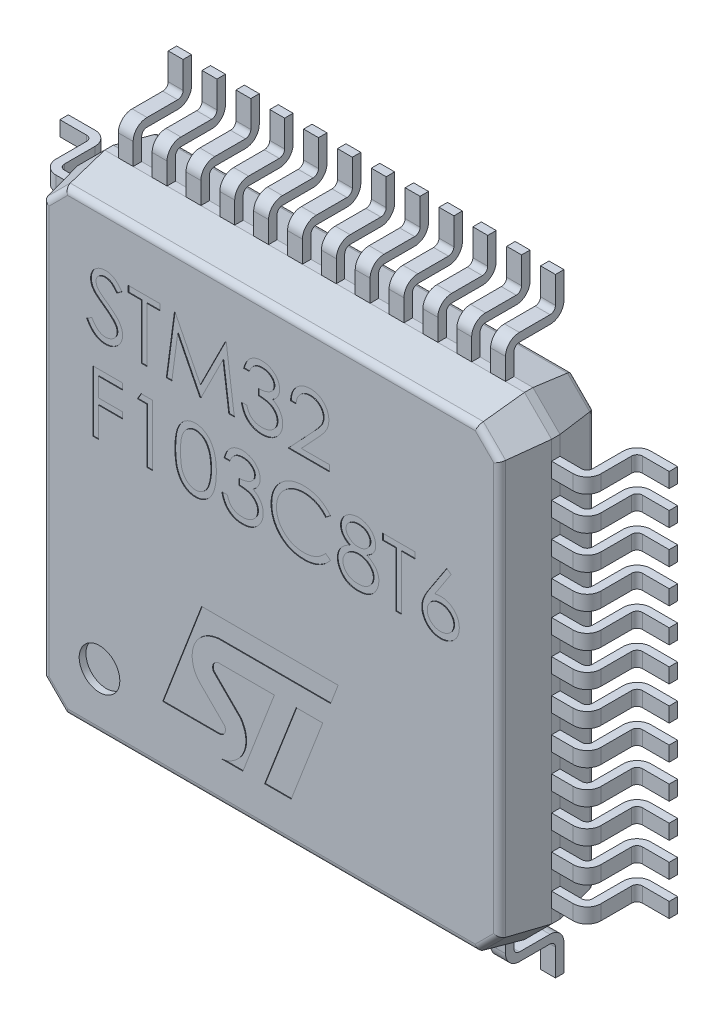
SolidWorks part; units mm, degrees
ref_plane "Front Plane" through (0, 0, 0) normal (0, 0, 1) x (1, 0, 0)
ref_plane "Top Plane" through (0, 0, 0) normal (0, 1, 0) x (1, 0, 0)
ref_plane "Right Plane" through (0, 0, 0) normal (1, 0, 0) x (0, 0, -1)
ref_plane "Plane1" through (0, 0, 0.1) normal (0, 0, 1) x (1, 0, 0)
sketch "Sketch1" plane through (0, 0, 0.1) normal (0, 0, 1) x (1, 0, 0)
  line L0 (-3.1, 3.5) -> (-3.5, 3.1)
  line L1 (-3.1, 3.5) -> (3.1, 3.5)
  line L2 (-3.5, 3.1) -> (-3.5, -3.1)
  line L3 (-3.1, -3.5) -> (3.1, -3.5)
  line L4 (3.5, 3.1) -> (3.5, -3.1)
  line L5 (-3.5, -3.1) -> (-3.1, -3.5)
  line L6 (3.1, -3.5) -> (3.5, -3.1)
  line L7 (3.1, 3.5) -> (3.5, 3.1)
extrude "Extrude1" add sketch "Sketch1" along normal blind 1.4
chamfer "Chamfer1" distance 0.6375 angle 12 16 edges at (-3.3, 3.3, 1.5) (0, 3.5, 1.5) (3.3, 3.3, 1.5) (3.5, 0, 1.5) (3.3, -3.3, 1.5) (0, -3.5, 1.5) (-3.3, -3.3, 1.5) (-3.5, 0, 1.5) (-3.3, -3.3, 0.1) (0, -3.5, 0.1) (3.3, -3.3, 0.1) (3.5, 0, 0.1) (3.3, 3.3, 0.1) (0, 3.5, 0.1) (-3.3, 3.3, 0.1) (-3.5, 0, 0.1) first distance on face at (-3.3, 3.3, 0.8) first distance on face at (0, 3.5, 0.8) first distance on face at (3.3, 3.3, 0.8) first distance on face at (3.5, 0, 0.8) first distance on face at (3.3, -3.3, 0.8) first distance on face at (0, -3.5, 0.8) first distance on face at (-3.3, -3.3, 0.8) first distance on face at (-3.5, 0, 0.8)
fillet "Fillet1" radius 0.1 16 edges at (3.2042, 3.2042, 1.5) (3.3645, 0, 1.5) (3.2042, -3.2042, 1.5) (0, -3.3645, 1.5) (-3.2042, -3.2042, 1.5) (-3.3645, 0, 1.5) (-3.2042, 3.2042, 1.5) (0, 3.3645, 1.5) (3.2042, -3.2042, 0.1) (3.3645, 0, 0.1) (3.2042, 3.2042, 0.1) (0, 3.3645, 0.1) (-3.2042, 3.2042, 0.1) (-3.3645, 0, 0.1) (-3.2042, -3.2042, 0.1) (0, -3.3645, 0.1)
sketch "Sketch2" plane through (0, 0, 0) normal (0, 0, 1) x (1, 0, 0)
  line L0 (2.1, -3.5) -> (2.1, -4.5)
  line L2 (2.6, -3.5) -> (2.82, -3.5)
  line L3 (2.6, -3.5) -> (2.6, -4.5)
  line L4 (2.6, -4.5) -> (2.82, -4.5)
  line L5 (2.82, -3.5) -> (2.82, -4.5)
  line L6 (2.32, -3.5) -> (2.32, -4.5)
  line L7 (2.1, -3.5) -> (2.32, -3.5)
  line L8 (2.1, -4.5) -> (2.32, -4.5)
  line L9 (1.6, -3.5) -> (1.6, -4.5)
  line L10 (1.82, -3.5) -> (1.82, -4.5)
  line L11 (1.6, -3.5) -> (1.82, -3.5)
  line L12 (1.6, -4.5) -> (1.82, -4.5)
  line L13 (1.1, -3.5) -> (1.1, -4.5)
  line L14 (1.32, -3.5) -> (1.32, -4.5)
  line L15 (1.1, -3.5) -> (1.32, -3.5)
  line L16 (1.1, -4.5) -> (1.32, -4.5)
  line L17 (0.6, -3.5) -> (0.6, -4.5)
  line L18 (0.82, -3.5) -> (0.82, -4.5)
  line L19 (0.6, -3.5) -> (0.82, -3.5)
  line L20 (0.6, -4.5) -> (0.82, -4.5)
  line L21 (0.1, -3.5) -> (0.1, -4.5)
  line L22 (0.32, -3.5) -> (0.32, -4.5)
  line L23 (0.1, -3.5) -> (0.32, -3.5)
  line L24 (0.1, -4.5) -> (0.32, -4.5)
  line L25 (-0.4, -3.5) -> (-0.4, -4.5)
  line L26 (-0.18, -3.5) -> (-0.18, -4.5)
  line L27 (-0.4, -3.5) -> (-0.18, -3.5)
  line L28 (-0.4, -4.5) -> (-0.18, -4.5)
  line L29 (-0.9, -3.5) -> (-0.9, -4.5)
  line L30 (-0.68, -3.5) -> (-0.68, -4.5)
  line L31 (-0.9, -3.5) -> (-0.68, -3.5)
  line L32 (-0.9, -4.5) -> (-0.68, -4.5)
  line L33 (-1.4, -3.5) -> (-1.4, -4.5)
  line L34 (-1.18, -3.5) -> (-1.18, -4.5)
  line L35 (-1.4, -3.5) -> (-1.18, -3.5)
  line L36 (-1.4, -4.5) -> (-1.18, -4.5)
  line L37 (-1.9, -3.5) -> (-1.9, -4.5)
  line L38 (-1.68, -3.5) -> (-1.68, -4.5)
  line L39 (-1.9, -3.5) -> (-1.68, -3.5)
  line L40 (-1.9, -4.5) -> (-1.68, -4.5)
  line L41 (-2.4, -3.5) -> (-2.4, -4.5)
  line L42 (-2.18, -3.5) -> (-2.18, -4.5)
  line L43 (-2.4, -3.5) -> (-2.18, -3.5)
  line L44 (-2.4, -4.5) -> (-2.18, -4.5)
  line L45 (-2.9, -3.5) -> (-2.9, -4.5)
  line L46 (-2.68, -3.5) -> (-2.68, -4.5)
  line L47 (-2.9, -3.5) -> (-2.68, -3.5)
  line L48 (-2.9, -4.5) -> (-2.68, -4.5)
  dimension "D1" = 12
extrude "Extrude2" add sketch "Sketch2" along normal blind 0.8625
sketch "Sketch3" plane through (2.82, 0, 0) normal (1, 0, 0) x (0, 0, -1)
  line L0 (-0.6575, -3.9) -> (-0.205, -3.9)
  line L1 (-0.8625, -3.82) -> (-0.8625, -4.5)
  line L2 (-0.8625, -4.5) -> (-0.125, -4.5)
  line L3 (-0.7375, -3.5) -> (0, -3.5)
  line L4 (-0.7375, -3.5) -> (-0.7375, -3.82)
  line L5 (0, -3.5) -> (0, -4.105)
  line L6 (-0.125, -4.105) -> (-0.125, -4.5)
  line L7 (-0.6575, -4.025) -> (-0.205, -4.025)
  line L8 (-0.8625, -4.5) -> (0, -4.5) construction
  arc A0 (-0.7375, -3.82) -> (-0.6575, -3.9) centre (-0.6575, -3.82) ccw
  arc A1 (-0.8625, -3.82) -> (-0.6575, -4.025) centre (-0.6575, -3.82) ccw
  arc A2 (-0.125, -4.105) -> (-0.205, -4.025) centre (-0.205, -4.105) ccw
  arc A3 (0, -4.105) -> (-0.205, -3.9) centre (-0.205, -4.105) ccw
extrude "Extrude3" cut sketch "Sketch3" against normal through all
mirror "Mirror1" about plane through (0, 0, 0) normal (0, 1, 0) of "Extrude3", "Extrude2"
sketch "Sketch4" plane through (0, 0, 0) normal (0, 0, 1) x (1, 0, 0)
  line L1 (-3.5, -2.18) -> (-4.5, -2.18)
  line L2 (-4.5, -2.18) -> (-4.5, -2.4)
  line L3 (-3.5, -2.4) -> (-4.5, -2.4)
  line L4 (-3.5, -2.18) -> (-3.5, -2.4)
  line L5 (-3.5, -1.68) -> (-4.5, -1.68)
  line L6 (-4.5, -1.68) -> (-4.5, -1.9)
  line L7 (-3.5, -1.9) -> (-4.5, -1.9)
  line L8 (-3.5, -1.68) -> (-3.5, -1.9)
  line L9 (-3.5, -1.18) -> (-4.5, -1.18)
  line L10 (-4.5, -1.18) -> (-4.5, -1.4)
  line L11 (-3.5, -1.4) -> (-4.5, -1.4)
  line L12 (-3.5, -1.18) -> (-3.5, -1.4)
  line L13 (-3.5, -0.68) -> (-4.5, -0.68)
  line L14 (-4.5, -0.68) -> (-4.5, -0.9)
  line L15 (-3.5, -0.9) -> (-4.5, -0.9)
  line L16 (-3.5, -0.68) -> (-3.5, -0.9)
  line L17 (-3.5, -0.18) -> (-4.5, -0.18)
  line L18 (-4.5, -0.18) -> (-4.5, -0.4)
  line L19 (-3.5, -0.4) -> (-4.5, -0.4)
  line L20 (-3.5, -0.18) -> (-3.5, -0.4)
  line L21 (-3.5, 0.32) -> (-4.5, 0.32)
  line L22 (-4.5, 0.32) -> (-4.5, 0.1)
  line L23 (-3.5, 0.1) -> (-4.5, 0.1)
  line L24 (-3.5, 0.32) -> (-3.5, 0.1)
  line L25 (-3.5, 0.82) -> (-4.5, 0.82)
  line L26 (-4.5, 0.82) -> (-4.5, 0.6)
  line L27 (-3.5, 0.6) -> (-4.5, 0.6)
  line L28 (-3.5, 0.82) -> (-3.5, 0.6)
  line L29 (-3.5, 1.32) -> (-4.5, 1.32)
  line L30 (-4.5, 1.32) -> (-4.5, 1.1)
  line L31 (-3.5, 1.1) -> (-4.5, 1.1)
  line L32 (-3.5, 1.32) -> (-3.5, 1.1)
  line L33 (-3.5, 1.82) -> (-4.5, 1.82)
  line L34 (-4.5, 1.82) -> (-4.5, 1.6)
  line L35 (-3.5, 1.6) -> (-4.5, 1.6)
  line L36 (-3.5, 1.82) -> (-3.5, 1.6)
  line L37 (-3.5, 2.32) -> (-4.5, 2.32)
  line L38 (-4.5, 2.32) -> (-4.5, 2.1)
  line L39 (-3.5, 2.1) -> (-4.5, 2.1)
  line L40 (-3.5, 2.32) -> (-3.5, 2.1)
  line L41 (-3.5, -2.68) -> (-4.5, -2.68)
  line L42 (-4.5, -2.68) -> (-4.5, -2.9)
  line L43 (-3.5, -2.9) -> (-4.5, -2.9)
  line L44 (-3.5, -2.68) -> (-3.5, -2.9)
  line L45 (-3.5, 2.82) -> (-4.5, 2.82)
  line L46 (-4.5, 2.82) -> (-4.5, 2.6)
  line L47 (-3.5, 2.6) -> (-4.5, 2.6)
  line L48 (-3.5, 2.82) -> (-3.5, 2.6)
  dimension "D1" = 12
extrude "Extrude4" add sketch "Sketch4" along normal blind 0.8625
sketch "Sketch5" plane through (0, -2.9, 0) normal (0, -1, 0) x (1, 0, 0)
  line L0 (-3.9, 0.6575) -> (-3.9, 0.205)
  line L4 (-3.5, 0.7375) -> (-3.82, 0.7375)
  line L6 (-4.5, 0.125) -> (-4.105, 0.125)
  line L7 (-4.5, 0.8625) -> (-4.5, 0) construction
  line L8 (-4.025, 0.6575) -> (-4.025, 0.205)
  line L9 (-3.5, 0.7375) -> (-3.5, 0)
  line L10 (-3.5, 0) -> (-4.105, 0)
  line L11 (-3.82, 0.8625) -> (-4.5, 0.8625)
  line L12 (-4.5, 0.8625) -> (-4.5, 0.125)
  arc A0 (-3.82, 0.7375) -> (-3.9, 0.6575) centre (-3.82, 0.6575) ccw
  arc A1 (-3.82, 0.8625) -> (-4.025, 0.6575) centre (-3.82, 0.6575) ccw
  arc A2 (-4.025, 0.205) -> (-4.105, 0.125) centre (-4.105, 0.205) cw
  arc A3 (-3.9, 0.205) -> (-4.105, 0) centre (-4.105, 0.205) cw
extrude "Extrude5" cut sketch "Sketch5" against normal through all
mirror "Mirror2" about plane through (0, 0, 0) normal (1, 0, 0) of "Extrude5", "Extrude4"
sketch "Sketch6" plane through (0, 0, 1.5) normal (0, 0, 1) x (1, 0, 0)
  line L0 (-2.54, -3.5) -> (-2.54, -2.54) construction
  line L2 (-3.5, -2.54) -> (-2.54, -2.54) construction
  line L5 (-2.4, -3.5) -> (-2.68, -3.5) construction
  line L6 (-3.5, -2.68) -> (-3.5, -2.4) construction
  circle A0 centre (-2.54, -2.54) radius 0.3
extrude "Extrude6" cut sketch "Sketch6" against normal blind 0.1
sketch "Sketch7" plane through (0, 0, 1.5) normal (0, 0, 1) x (1, 0, 0)
  line L0 (-92.313, 157.0393) -> (404.3537, 157.0393) construction
  line L1 (0.985, -0.9845) -> (-1.0308, -0.9845)
  line L2 (-1.0308, -0.9845) -> (-1.6061, -2.4866)
  line L3 (-1.6061, -2.4866) -> (-0.7782, -2.4866)
  line L4 (-0.6974, -2.3345) -> (-1.0656, -1.9663)
  line L5 (-0.7782, -1.2738) -> (0.8744, -1.2738)
  line L6 (0.8744, -1.2738) -> (0.985, -0.9845)
  line L7 (-0.4212, -2.7876) -> (0.043, -1.5816)
  line L8 (0.043, -1.5816) -> (-0.7708, -1.5816)
  line L9 (-0.8556, -1.7319) -> (-0.4573, -2.1301)
  line L10 (-0.7369, -2.7876) -> (-0.4212, -2.7876)
  line L11 (0.3663, -1.5816) -> (0.7577, -1.5816)
  line L12 (0.7577, -1.5816) -> (0.2918, -2.7876)
  line L13 (0.2918, -2.7876) -> (-0.1004, -2.7876)
  line L14 (-0.1004, -2.7876) -> (0.3663, -1.5816)
  spline S0 degree 3 poles (-0.7782, -2.4866) (-0.745, -2.4865) (-0.6961, -2.4598) (-0.6752, -2.3906) (-0.6833, -2.3526) (-0.6974, -2.3345) knots 0 0 0 0 0.478706 0.677314 1 1 1 1
  spline S1 degree 3 poles (-1.0656, -1.9663) (-1.1063, -1.9235) (-1.1515, -1.841) (-1.1766, -1.6971) (-1.1647, -1.573) (-1.108, -1.4577) (-1.0171, -1.3509) (-0.8945, -1.2918) (-0.8043, -1.277) (-0.7782, -1.2738) knots 0 0 0 0 0.18983 0.294522 0.468646 0.580629 0.704401 0.915479 1 1 1 1
  spline S2 degree 3 poles (-0.7708, -1.5816) (-0.792, -1.5806) (-0.8321, -1.5939) (-0.8749, -1.6535) (-0.8692, -1.7058) (-0.8556, -1.7319) knots 0 0 0 0 0.305418 0.574312 1 1 1 1
  spline S3 degree 3 poles (-0.4573, -2.1301) (-0.4192, -2.186) (-0.3769, -2.2888) (-0.3752, -2.4432) (-0.4146, -2.5688) (-0.4907, -2.6692) (-0.5971, -2.7515) (-0.6825, -2.7844) (-0.7369, -2.7876) knots 0 0 0 0 0.236781 0.37815 0.532396 0.688336 0.810695 1 1 1 1
extrude "Cut-Extrude1" cut sketch "Sketch7" against normal blind 0.01
sketch "Sketch8" plane through (0, 0, 1.5) normal (0, 0, 1) x (1, 0, 0)
  text T0 "STM32" font "Century Gothic" height 0.9
  text T1 "F103C8T6" font "Century Gothic" height 0.9
extrude "Cut-Extrude2" cut sketch "Sketch8" against normal blind 0.01
